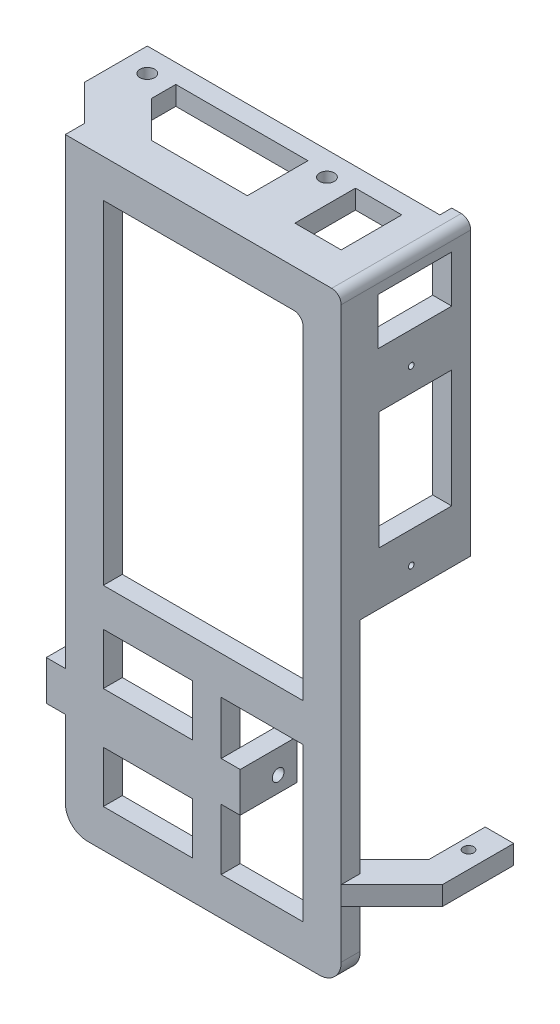
SolidWorks part; units mm, degrees
ref_plane "前视基准面" through (0, 0, 0) normal (0, 0, 1) x (1, 0, 0)
ref_plane "上视基准面" through (0, 0, 0) normal (0, 1, 0) x (1, 0, 0)
ref_plane "右视基准面" through (0, 0, 0) normal (1, 0, 0) x (0, 0, -1)
other "Configuration Table"
sketch "草图4" plane through (37.65, 0, 0) normal (1, 0, 0) x (0, 0, -1)
  line L1 (7.255, 53.1366) -> (23.255, 53.1366) construction
  line L2 (19.8734, 110.55) -> (11.6366, 110.55)
  line L3 (23.255, 110.55) -> (0, 110.55)
  line L4 (0, 53.1366) -> (23.255, 53.1366)
  line L5 (0, 110.55) -> (0, 53.1366)
  line L6 (23.255, 110.55) -> (23.255, 53.1366)
  line L7 (19.8734, 109.55) -> (11.6366, 109.55) construction
  line L8 (0, -7.25) -> (0, 31.75) construction
  line L9 (19.8734, 109.55) -> (11.6366, 109.55)
  line L11 (23.255, 107.6634) -> (23.255, 53.1366) construction
  circle A0 centre (10.735, 94.05) radius 0.6
  circle A1 centre (10.735, 57.65) radius 0.6
  point P17 (0, 0)
  circle M6 centre (10.735, 57.65) radius 1.1
  circle M7 centre (10.735, 62.275) radius 0.975
  circle M8 centre (10.735, 94.05) radius 1.1
  arc M9 (11.735, 97.8871) -> (9.735, 97.8871) centre (10.735, 98.67) cw
  line M10 (9.735, 97.8871) -> (9.735, 99.4529)
  arc M11 (9.735, 99.4529) -> (11.735, 99.4529) centre (10.735, 98.67) cw
  line M12 (11.735, 99.4529) -> (11.735, 97.8871)
  line M13 (7.255, 53.1366) -> (23.255, 53.1366)
  line M15 (23.255, 107.6634) -> (7.255, 107.6634)
  line M16 (7.255, 107.6634) -> (7.255, 53.1366)
  dimension "D2" = 1.2
  dimension "D1" = 1
extrude "凸台-拉伸5" add sketch "草图4" along normal blind 4 separate body contours A0 M8 | M9 M12 M11 M10 | L6 L3 L5 L4 M16 M15 | A1 M6 | L6 M15 M16 M13 M7 M12 M9 M10 M11 M8 M6 | M7 region at (37.65, 84.5646, -4.7881) region at (37.65, 80.4078, -15.3345) region at (37.65, 57.65, -9.6661) region at (37.65, 62.275, -10.735) region at (37.65, 94.05, -9.6661) region at (37.65, 98.67, -10.735)
sketch "草图5" plane through (0, 110.55, 0) normal (0, 1, 0) x (1, 0, 0)
  line L1 (41.65, 0) -> (37.65, 0) construction
  line L2 (41.65, 20.755) -> (-23.9, 20.755)
  line L3 (41.65, 20.755) -> (41.65, 0)
  line L4 (41.65, 0) -> (-23.9, 0)
  line L5 (-23.9, 20.755) -> (-23.9, 0)
  line L6 (41.65, 23.255) -> (41.65, 0) construction
  circle A0 centre (-18.9, 15.755) radius 1.55
  circle A1 centre (18.9, 15.755) radius 1.55
  point P13 (0, 0)
  point P14 (41.65, 19.8734)
  dimension "D2" = 3.1
  dimension "D1" = 5
  dimension "D3" = 5
extrude "凸台-拉伸6" add sketch "草图5" along normal blind 4
sketch "草图7" plane through (0, 0, 0) normal (0, 0, 1) x (1, 0, 0)
  line L0 (41.65, 114.55) -> (41.65, 53.1366) construction
  line L6 (-11.75, -11.9) -> (11.75, -11.9) construction
  line L7 (-23.9, 114.55) -> (41.65, 114.55)
  line L8 (-23.9, 114.55) -> (-23.9, -11.9)
  line L9 (-23.9, -11.9) -> (41.65, -11.9)
  line L10 (41.65, 114.55) -> (41.65, -11.9)
extrude "凸台-拉伸8" add sketch "草图7" along normal blind 4
sketch "草图11" plane through (0, 0, 0) normal (0, 0, -1) x (-1, 0, 0)
  line L0 (-33.65, -3.9) -> (-33.65, 110.55)
  line L1 (-33.65, -3.9) -> (8.4, -3.9)
  line L3 (8.4, -3.9) -> (8.4, 110.55)
  line L4 (-37.65, 110.55) -> (23.9, 110.55) construction
  line L5 (23.9, -11.9) -> (-41.65, -11.9) construction
  line L6 (16.4, -7.25) -> (16.4, 21.75) construction
  line L7 (-10.4, -3.9) -> (-10.4, 28.4)
  line L8 (-10.4, 28.4) -> (8.4, 28.4)
  line L9 (8.4, 28.4) -> (8.4, 36.4)
  line L10 (8.4, 36.4) -> (-16.4, 36.4)
  line L11 (-16.4, 36.4) -> (-16.4, -3.9)
  line L12 (-16.4, 60.55) -> (-16.4, 21.75) construction
  line L13 (11.32, 36.4) -> (-11.32, 36.4) construction
  line L14 (8.4, 6.9) -> (-10.4, 6.9)
  line L15 (-10.4, 17.6) -> (8.4, 17.6)
  line L16 (9.52, 15.6) -> (-9.52, 15.6) construction
  line L17 (-11.32, 8.9) -> (11.32, 8.9) construction
  line L18 (-16.4, 60.55) -> (-16.4, -7.25) construction
  line L19 (-10.73, -11.9) -> (10.73, -11.9) construction
  line L20 (-16.4, 60.55) -> (-16.4, -7.25)
  line L21 (-11.75, -11.9) -> (11.75, -11.9)
  line L22 (16.4, -7.25) -> (16.4, 31.75)
  line L23 (8.4, 36.4) -> (11.75, 36.4)
  line L24 (16.4, 31.75) -> (16.4, 110.55)
  line L25 (23.9, 110.55) -> (-37.65, 110.55) construction
  line L26 (8.4, 110.55) -> (23.9, 110.55)
  line L27 (23.9, 110.55) -> (23.9, -11.9) construction
  line L28 (23.9, 110.55) -> (23.9, -11.9)
  line L29 (23.9, -11.9) -> (-41.65, -11.9)
  line L30 (-33.65, 110.55) -> (23.9, 110.55)
  line L31 (-41.65, -11.9) -> (-41.65, 53.1366) construction
  line L32 (23.9, 106.55) -> (-33.65, 106.55)
  line L33 (-41.65, 114.55) -> (23.9, 114.55) construction
  line L34 (-10.4, 28.4) -> (-33.65, 28.4)
  line L35 (-16.4, 36.4) -> (-33.65, 36.4)
  arc A0 (16.4, 31.75) -> (11.75, 36.4) centre (11.75, 31.75) ccw construction
  arc A1 (-16.4, -7.25) -> (-11.75, -11.9) centre (-11.75, -7.25) ccw construction
  arc A2 (11.75, -11.9) -> (16.4, -7.25) centre (11.75, -7.25) ccw construction
  arc A3 (16.4, 31.75) -> (11.75, 36.4) centre (11.75, 31.75) ccw
  arc A4 (-16.4, -7.25) -> (-11.75, -11.9) centre (-11.75, -7.25) ccw
  arc A5 (11.75, -11.9) -> (16.4, -7.25) centre (11.75, -7.25) ccw
  point P51 (-16.4, 28.4)
  line M8 (-41.65, -11.9) -> (23.9, -11.9)
  line M9 (23.9, -11.9) -> (23.9, 110.55)
  dimension "D1" = 8
  dimension "D2" = 8
  dimension "D3" = 8
  dimension "D4" = 6
  dimension "D5" = 2
  dimension "D6" = 2
  dimension "D7" = 8
  dimension "D8" = 8
extrude "切除-拉伸3" cut sketch "草图11" against normal through all contours L3 L32 L0 L1 L11 L10 | L7 L15 L3 L8 | L3 L14 L7 L1 | A5 L32 L24 L22 M8 M9 | L11 L34 L0 L1 region at (25.025, 12.25, 0) region at (12.625, 71.475, 0) region at (1, 1.5, 0) region at (1, 23, 0) region at (-20.1251, 47.0227, 0)
sketch "草图12" plane through (0, 2.8903, 0) normal (0, 1, 0) x (1, 0, 0)
  line L0 (52.2958, 21.655) -> (52.2958, 9.855)
  line L1 (46.2958, 9.855) -> (36.4408, 0)
  line L2 (-11.75, 0) -> (41.65, 0) construction
  line L3 (52.2958, 9.855) -> (52.2958, 6.6458)
  line L5 (52.2958, 6.6458) -> (41.65, -4)
  line L6 (36.4408, 0) -> (41.65, -4)
  line L7 (50.9958, 9.855) -> (50.9958, 15.105)
  line L8 (50.9958, 15.105) -> (49.4557, 15.105)
  line L9 (49.4557, 16.405) -> (50.9958, 16.405)
  line L10 (50.9958, 16.405) -> (50.9958, 21.655)
  line L11 (50.9958, 21.655) -> (46.2958, 21.655)
  line L12 (46.2958, 21.655) -> (46.2958, 9.855)
  line L13 (46.2958, 9.855) -> (50.9958, 9.855)
  line L18 (52.2958, 21.655) -> (46.2958, 21.655)
  line L19 (46.2958, 21.655) -> (46.2958, 9.855)
  line L20 (46.2958, 9.855) -> (52.2958, 9.855)
  arc A1 (49.4557, 16.405) -> (49.4557, 15.105) centre (48.6958, 15.755) ccw
  point P7 (41.4147, -5.7128)
  line M13 (50.9958, 9.855) -> (50.9958, 15.105)
  line M14 (50.9958, 15.105) -> (49.4557, 15.105)
  arc M15 (49.4557, 15.105) -> (49.4557, 16.405) centre (48.6958, 15.755) cw
  line M16 (49.4557, 16.405) -> (50.9958, 16.405)
  line M17 (50.9958, 16.405) -> (50.9958, 21.655)
  line M18 (50.9958, 21.655) -> (46.2958, 21.655)
  line M19 (46.2958, 21.655) -> (46.2958, 9.855)
  line M20 (46.2958, 9.855) -> (50.9958, 9.855)
  dimension "D2" = 6
  dimension "D3" = 45
  dimension "D1" = 0
extrude "凸台-拉伸9" add sketch "草图12" along normal blind 4 contours M20 M13 M14 M15 M16 M17 M18 M19 | L20 L1 L6 L5 L3 M20 | L20 L0 L18 M13 M17 M16 M15 M14 region at (51.0703, 2.8903, -15.755) region at (44.7702, 2.8903, -3.628) region at (50.8687, 2.8903, -19.03)
sketch "草图13" plane through (0, 110.55, 0) normal (0, -1, 0) x (1, 0, 0)
  line L0 (-23.9, -7.5) -> (-16.4, 0)
  line L1 (-23.9, -20.755) -> (-23.9, 0) construction
  line L4 (-16.4, 4) -> (-16.4, 0) construction
  line L5 (-16.4, 4) -> (-16.4, 0)
  line L6 (-16.4, 4) -> (-23.9, 4)
  line L7 (-23.9, 4) -> (-23.9, -7.5)
  dimension "D1" = 45
extrude "切除-拉伸4" cut sketch "草图13" against normal mid plane 20
sketch "草图14" plane through (0, 110.55, 0) normal (0, -1, 0) x (1, 0, 0)
  line L0 (37.65, -20.755) -> (-23.9, -20.755) construction
  line L1 (33.65, -16.755) -> (23.9, -16.755)
  line L2 (33.65, -16.755) -> (33.65, -4)
  line L3 (33.65, -4) -> (23.9, -4)
  line L4 (23.9, -16.755) -> (23.9, -4)
  line L5 (13.9, -16.755) -> (-13.9, -16.755)
  line L6 (13.9, -16.755) -> (13.9, -4)
  line L7 (13.9, -4) -> (-6.2579, -4)
  line L8 (-13.9, -16.755) -> (-13.9, -11.6421)
  line L10 (-8.4, 0) -> (33.65, 0) construction
  line L11 (-13.9, -11.6421) -> (-6.2579, -4)
  line L12 (-23.9, -7.5) -> (-16.4, 0) construction
  line L13 (37.65, -20.755) -> (37.65, 0) construction
  circle A0 centre (18.9, -15.755) radius 1.55 construction
  circle A1 centre (-18.9, -15.755) radius 1.55 construction
  dimension "D4" = 5
  dimension "D1" = 4
  dimension "D2" = 4
  dimension "D3" = 4
  dimension "D5" = 5
  dimension "D6" = 5
  dimension "D7" = 10
extrude "切除-拉伸5" cut sketch "草图14" against normal blind 10
sketch "草图16" plane through (37.65, 0, 0) normal (-1, 0, 0) x (0, 0, 1)
  line L1 (-19.255, 64.275) -> (-4, 64.275)
  line L2 (-19.255, 64.275) -> (-19.255, 89.05)
  line L3 (-19.255, 89.05) -> (-4, 89.05)
  line L4 (-4, 64.275) -> (-4, 89.05)
  line L5 (0, -7.25) -> (0, 110.55) construction
  line L6 (-7.5, 110.55) -> (0, 110.55) construction
  line L7 (-19.255, 100.67) -> (-3.75, 100.67)
  line L8 (-19.255, 100.67) -> (-19.255, 110.55)
  line L9 (-19.255, 110.55) -> (-3.75, 110.55)
  line L10 (-3.75, 100.67) -> (-3.75, 110.55)
  line L11 (-23.255, 110.55) -> (-23.255, 53.1366) construction
  circle A0 centre (-10.735, 62.275) radius 0.975 construction
  circle A1 centre (-10.735, 94.05) radius 1.1 construction
  arc A2 (-9.735, 99.4529) -> (-11.735, 99.4529) centre (-10.735, 98.67) ccw construction
  point P18 (-19.2189, 102.8615)
  dimension "D1" = 4
  dimension "D2" = 4
  dimension "D3" = 2
  dimension "D4" = 5
  dimension "D5" = 2
extrude "切除-拉伸6" cut sketch "草图16" against normal through all
sketch "草图17" plane through (37.65, 0, 0) normal (-1, 0, 0) x (0, 0, 1)
  line L0 (-11.735, 97.8871) -> (-11.735, 99.4529) construction
  line L1 (-9.735, 97.8871) -> (-9.735, 99.4529) construction
  line L2 (-11.735, 97.8871) -> (-11.735, 99.4529)
  line L3 (-9.735, 97.8871) -> (-9.735, 99.4529)
  line L4 (-11.635, 97.9224) -> (-11.635, 99.4176)
  line L5 (-9.835, 97.9224) -> (-9.835, 99.4176)
  arc A0 (-9.735, 99.4529) -> (-11.735, 99.4529) centre (-10.735, 98.67) ccw construction
  arc A1 (-11.735, 97.8871) -> (-9.735, 97.8871) centre (-10.735, 98.67) ccw construction
  circle A2 centre (-10.735, 62.275) radius 0.975 construction
  arc A3 (-9.735, 99.4529) -> (-11.735, 99.4529) centre (-10.735, 98.67) ccw
  arc A4 (-11.735, 97.8871) -> (-9.735, 97.8871) centre (-10.735, 98.67) ccw
  circle A5 centre (-10.735, 62.275) radius 0.975
  arc A6 (-9.835, 99.4176) -> (-11.635, 99.4176) centre (-10.735, 98.67) ccw
  arc A7 (-11.635, 97.9224) -> (-9.835, 97.9224) centre (-10.735, 98.67) ccw
  circle A8 centre (-10.735, 62.275) radius 0.875
  dimension "D1" = 0.1
extrude "凸台-拉伸10" add sketch "草图17" along normal blind 1 contours A8 | L4 A7 L5 A6 region at (37.65, 98.67, -10.735) region at (37.65, 62.275, -10.735)
fillet "圆角1" radius 0.5 5 edges at (36.65, 99.84, -10.735) (36.65, 98.67, -9.835) (36.65, 97.5, -10.735) (36.65, 98.67, -11.635) (36.65, 61.4, -10.735)
sketch "草图2" plane through (-16.4, 0, 0) normal (-1, 0, 0) x (0, 0, 1)
  line L1 (-11.22, 8.9) -> (-4.3571, 8.9) construction
  line L3 (-11.22, 8.9) -> (4, 8.9)
  line L16 (4, -7.25) -> (4, 114.55) construction
  line L17 (-11.22, 15.6) -> (0, 15.6) construction
  line L18 (-11.22, 15.6) -> (4, 15.6)
  line L19 (-8.4892, 12.25) -> (2.3386, 12.25) construction
  line L20 (4, 15.6) -> (4, 8.9)
  line L21 (4, 15.6) -> (4, 17.25)
  line L22 (4, 17.25) -> (-8, 17.25)
  line L23 (-8, 17.25) -> (-8, 8.9)
  line L24 (0, -7.25) -> (0, 110.55) construction
  circle A1 centre (-4, 12.25) radius 1.25
  arc M32 (-4.5, 8.55) -> (-4, 9.05) centre (-4, 8.55) cw
  line M33 (-4, 9.05) -> (0, 9.05)
  line M34 (0, 9.05) -> (0, 27.55)
  dimension "D2" = 5
  dimension "D4" = 4
  dimension "D1" = 2.5
  dimension "D3" = 4
extrude "凸台-拉伸2" add sketch "草图2" along normal blind 4 contours L20 L18 L3 M34 M33 M32 | L19 L23 L3 A1 M32 M33 M34 | L23 L19 A1 L18 M34 | L22 L23 L18 M34 | L21 L22 L18 M34 region at (-16.4, 10.4995, -4.0504) region at (-16.4, 12.174, 1.9043) region at (-16.4, 14.0404, -4) region at (-16.4, 16.425, -4) region at (-16.4, 16.425, 2)
mirror "镜向10" about plane through (0, 0, 0) normal (1, 0, 0) of "凸台-拉伸2"
sketch "草图19" plane through (0, 2.8903, 0) normal (0, -1, 0) x (1, 0, 0)
  circle A0 centre (48.6958, -15.755) radius 1.1
  arc A1 (49.4557, -15.105) -> (49.4557, -16.405) centre (48.6958, -15.755) ccw construction
  dimension "D1" = 2.2
extrude "切除-拉伸7" cut sketch "草图19" against normal up to next
sketch "草图21" plane through (0, 110.55, 0) normal (0, 1, 0) x (1, 0, 0)
  line L4 (37.65, 20.755) -> (41.65, 20.755)
  line L5 (41.65, 20.755) -> (41.65, 23.255)
  line L6 (41.65, 23.255) -> (37.65, 23.255)
  line L7 (37.65, 23.255) -> (37.65, 20.755)
  line L8 (37.65, 20.755) -> (41.65, 20.755)
  line L9 (41.65, 20.755) -> (41.65, 23.255)
  line L10 (41.65, 23.255) -> (37.65, 23.255)
  line L11 (37.65, 23.255) -> (37.65, 20.755)
  dimension "D1" = 0
extrude "凸台-拉伸11" add sketch "草图21" along normal up to surface (4 mm away) up to face at (28.775, 114.55, -10.3775)
fillet "圆角2" radius 2 4 edges at (41.65, 114.55, -9.6275) (33.65, 106.55, 2) (37.65, 110.55, -1.875) (37.65, 110.55, -20.005)
fillet "圆角3" radius 4.65 1 edges at (41.65, -11.9, 2)
